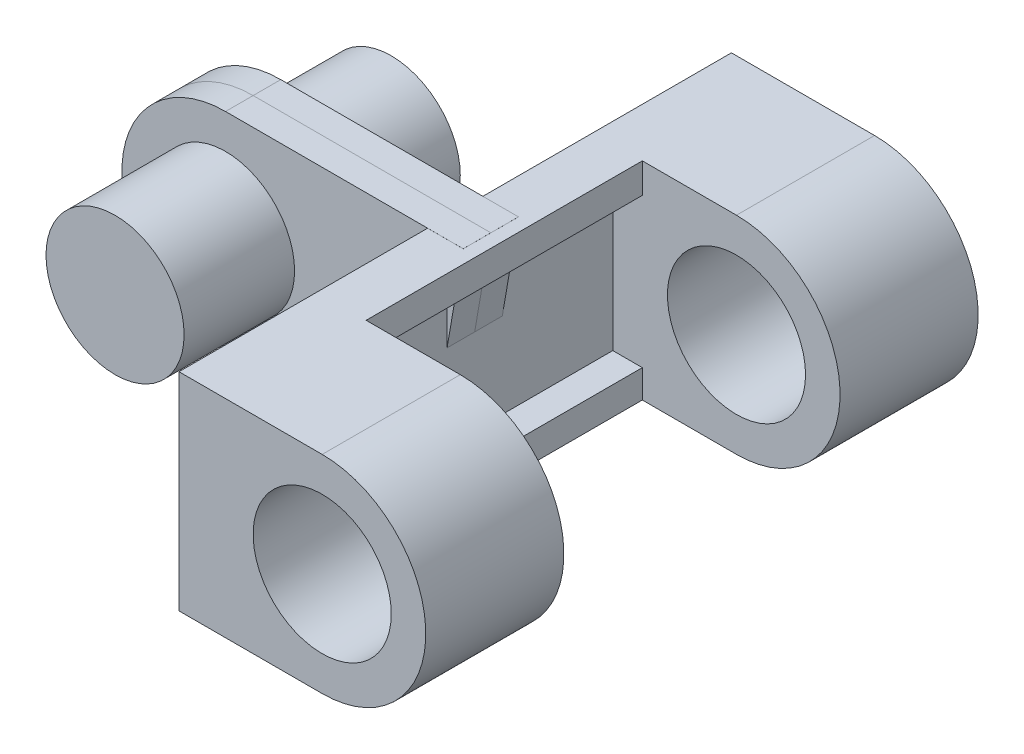
SolidWorks part; units mm, degrees
ref_plane "Front Plane" through (0, 0, 0) normal (0, 0, 1) x (1, 0, 0)
ref_plane "Top Plane" through (0, 0, 0) normal (0, 1, 0) x (1, 0, 0)
ref_plane "Right Plane" through (0, 0, 0) normal (1, 0, 0) x (0, 0, -1)
sketch "Sketch1" plane through (0, 0, 0) normal (0, 0, 1) x (1, 0, 0)
  line L0 (-2.5, 0) -> (0, 0) construction
  line L1 (-1.0368, 0.75) -> (0, 0.75)
  line L2 (-1.0368, -0.75) -> (0, -0.75)
  line L3 (-1.0368, 0.75) -> (-1.0368, -0.75)
  line L4 (-2.5266, 0.75) -> (-1.0368, 0.75) construction
  line L5 (-2.4734, -0.75) -> (-1.0368, -0.75) construction
  arc A0 (-2.5266, 0.75) -> (-2.4734, -0.75) centre (-2.5, 0) ccw construction
  arc A1 (0, -0.75) -> (0, 0.75) centre (0, 0) ccw
  circle A2 centre (-2.5, 0) radius 0.5 construction
  circle A3 centre (0, 0) radius 0.5
  point P1 (0.3221, -0.0047)
  point P2 (0, 0)
  point P14 (0, 0)
  point P15 (0, 0)
  point P16 (0, 0)
  point P17 (0, 0)
  point P18 (0, 0)
  point P19 (0, 0)
  point P21 (0.1965, -0.7453)
  point P22 (-1.061, -0.7328)
  point P23 (-0.7502, -0.75)
  point P24 (0, 0)
  point P25 (-1.7342, 0)
  point P26 (-1.0368, -0.75)
  point P27 (-2.4734, 0)
  dimension "D1" = 1
  dimension "D2" = 1.5
  dimension "D3" = 2.5
extrude "Boss-Extrude1" add sketch "Sketch1" along normal blind 1
sketch "Sketch2" plane through (0, 0, 1) normal (0, 0, 1) x (1, 0, 0)
  line L0 (-0.6819, 0.75) -> (-1.0368, 0.75)
  line L1 (-1.0368, 0.75) -> (-1.0368, -0.75)
  line L2 (-1.0368, -0.75) -> (-0.6819, -0.75)
  line L6 (-0.6819, -0.75) -> (-0.6819, -0.5468)
  line L12 (-0.6819, -0.5468) -> (-0.8957, -0.5468)
  line L13 (-0.8957, -0.5468) -> (-0.8957, 0.5335)
  line L14 (-0.8957, 0.5335) -> (-0.6819, 0.5335)
  line L15 (-0.6819, 0.5335) -> (-0.6819, 0.75)
  arc A9 (-0.1916, -0.5916) -> (-0.6819, 0.5335) centre (-0.2403, 0.0565) ccw construction
  point P2 (0, 0)
  point P8 (-0.5412, -0.75)
  point P9 (-0.7827, -0.3831)
  point P10 (-0.9098, -0.6052)
  point P11 (-0.7461, -0.6052)
  point P12 (0, 0)
extrude "Boss-Extrude2" add sketch "Sketch2" along normal blind 1 contours L15 L0 L1 L2 L6 L12 L13 L14
ref_plane "Plane6" through (0, 0, 2) normal (0, 0, 1) x (1, 0, 0)
mirror "Mirror4" about plane through (0, 0, 2) normal (0, 0, 1) of bodies 103
sketch "Sketch4" plane through (0, 0, 2) normal (0, 0, 1) x (1, 0, 0)
  line L0 (-0.7787, 0.7503) -> (-2.4999, 0.7505)
  line L1 (-2.4998, -0.7505) -> (-1.0368, -0.75)
  line L3 (-0.7787, 0.7503) -> (-1.0368, -0.75)
  circle A0 centre (-2.5, 0) radius 0.5 construction
  circle A1 centre (-2.5, 0) radius 0.5 construction
  arc A2 (-2.4999, 0.7505) -> (-2.4998, -0.7505) centre (-2.5, 0) ccw
  arc A3 (-2.5266, 0.75) -> (-2.4734, -0.75) centre (-2.5, 0) ccw construction
extrude "Boss-Extrude4" add sketch "Sketch4" along normal blind 0.2 separate body
sketch "Sketch5" plane through (0, 0, 2) normal (0, 0, -1) x (-1, 0, 0)
  circle A0 centre (2.5, 0) radius 0.5
  circle A1 centre (2.5, 0) radius 0.5 construction
extrude "Boss-Extrude5" add sketch "Sketch5" along normal blind 1
mirror "Mirror5" about plane through (0, 0, 2) normal (0, 0, 1) of bodies 109
ref_axis "Axis1" through (-2.5, 0, 3) along (0, 0, -1)
ref_axis "Axis2" through (0, 0, 4.2) along (0, 0, -1)
